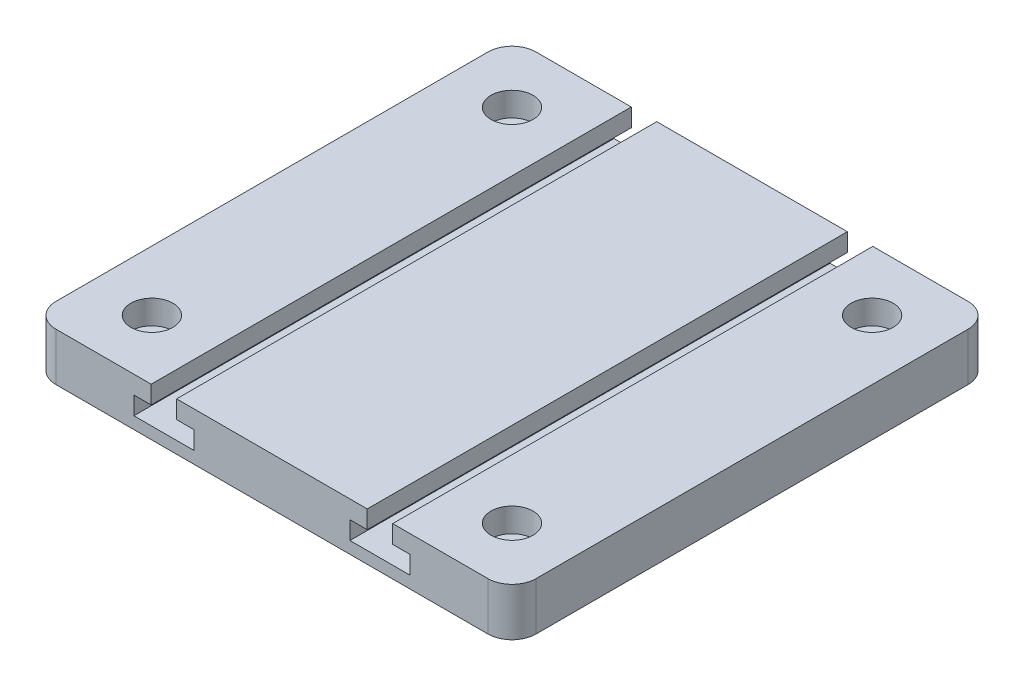
SolidWorks part; units mm, degrees
material "Delrin 2700 NC010, Low Viscosity Acetal Copolymer (SS)"
ref_plane "Front" through (0, 0, 0) normal (0, 0, 1) x (1, 0, 0)
ref_plane "Top" through (0, 0, 0) normal (0, 1, 0) x (1, 0, 0)
ref_plane "Right" through (0, 0, 0) normal (1, 0, 0) x (0, 0, -1)
sketch "Sketch1" plane through (0, 0, 0) normal (0, 1, 0) x (1, 0, 0)
  line L1 (-63.5, 63.5) -> (63.5, 63.5)
  line L2 (-63.5, 63.5) -> (-63.5, -63.5)
  line L3 (-63.5, -63.5) -> (63.5, -63.5)
  line L4 (63.5, 63.5) -> (63.5, -63.5)
  line L5 (-63.5, 63.5) -> (63.5, -63.5) construction
  line L6 (-63.5, -63.5) -> (63.5, 63.5) construction
  point P0 (0, 0)
  dimension "D1" = 127
  dimension "D2" = 127
extrude "Boss-Extrude1" add sketch "Sketch1" along normal blind 12.7
hole_wizard "CBORE for 1/4 Socket Head Cap Screw1" positions "Sketch2" profile "Sketch3" counterbore size "1/4" standard "ANSI Inch" end condition through all
sketch "Sketch2" plane through (0, 12.7, 0) normal (0, 1, 0) x (1, 0, 0)
  line L1 (-47.625, 47.625) -> (47.625, 47.625) construction
  line L2 (-47.625, 47.625) -> (-47.625, -47.625) construction
  line L3 (-47.625, -47.625) -> (47.625, -47.625) construction
  line L4 (47.625, 47.625) -> (47.625, -47.625) construction
  line L5 (-47.625, 47.625) -> (47.625, -47.625) construction
  line L6 (-47.625, -47.625) -> (47.625, 47.625) construction
  point P0 (-47.625, 47.625)
  point P2 (47.625, 47.625)
  point P4 (47.625, -47.625)
  point P6 (-47.625, -47.625)
  point P108 (0, 0)
  dimension "D1" = 95.25
  dimension "D2" = 95.25
sketch "Sketch3" plane through (-47.625, 12.7, -47.625) normal (1, 0, 0) x (0, 0, 1)
  line L0 (0, 0) -> (0, 12.7)
  line L1 (0, 12.7) -> (3.2639, 12.7)
  line L3 (3.2639, 12.7) -> (3.2639, 6.35)
  line L4 (3.2639, 6.35) -> (5.5562, 6.35)
  line L5 (5.5562, 6.35) -> (5.5562, 0)
  line L7 (5.5562, 0) -> (0, 0)
  line L11 (0, -6.35) -> (0, 107.95) construction
  dimension "Thru Hole Dia." = 6.5278
  dimension "Thru Hole Depth" = 12.7
  dimension "C'Bore Dia." = 11.1125
  dimension "C'Bore Depth" = 6.35
sketch "Sketch4" plane through (0, 0, 63.5) normal (0, 0, 1) x (1, 0, 0)
  line L0 (-31.9405, 12.7) -> (-31.9405, 7.9375)
  line L1 (-63.5, 12.7) -> (63.5, 12.7) construction
  line L2 (-31.9405, 7.9375) -> (-36.5125, 7.9375)
  line L3 (-36.5125, 7.9375) -> (-36.5125, 3.175)
  line L4 (-36.5125, 3.175) -> (-20.6375, 3.175)
  line L5 (-20.6375, 3.175) -> (-20.6375, 7.9375)
  line L6 (-20.6375, 7.9375) -> (-25.2095, 7.9375)
  line L7 (-25.2095, 7.9375) -> (-25.2095, 12.7)
  line L8 (0, 0) -> (0, 12.7) construction
  line L9 (-28.575, 3.175) -> (-28.575, 12.7) construction
  line L10 (28.575, 3.175) -> (28.575, 12.7) construction
  line L11 (25.2095, 7.9375) -> (25.2095, 12.7)
  line L12 (20.6375, 7.9375) -> (25.2095, 7.9375)
  line L13 (20.6375, 3.175) -> (20.6375, 7.9375)
  line L14 (36.5125, 3.175) -> (20.6375, 3.175)
  line L15 (36.5125, 7.9375) -> (36.5125, 3.175)
  line L16 (31.9405, 7.9375) -> (36.5125, 7.9375)
  line L17 (31.9405, 12.7) -> (31.9405, 7.9375)
  line L18 (-31.9405, 12.7) -> (-25.2095, 12.7)
  line L19 (25.2095, 12.7) -> (31.9405, 12.7)
  dimension "D1" = 15.875
  dimension "D2" = 6.731
  dimension "D3" = 4.7625
  dimension "D4" = 57.15
  dimension "D5" = 4.7625
extrude "Cut-Extrude1" cut sketch "Sketch4" against normal through all
fillet "Fillet1" radius 6.35 4 edges at (-63.5, 6.35, 63.5) (63.5, 6.35, 63.5) (63.5, 6.35, -63.5) (-63.5, 6.35, -63.5)
